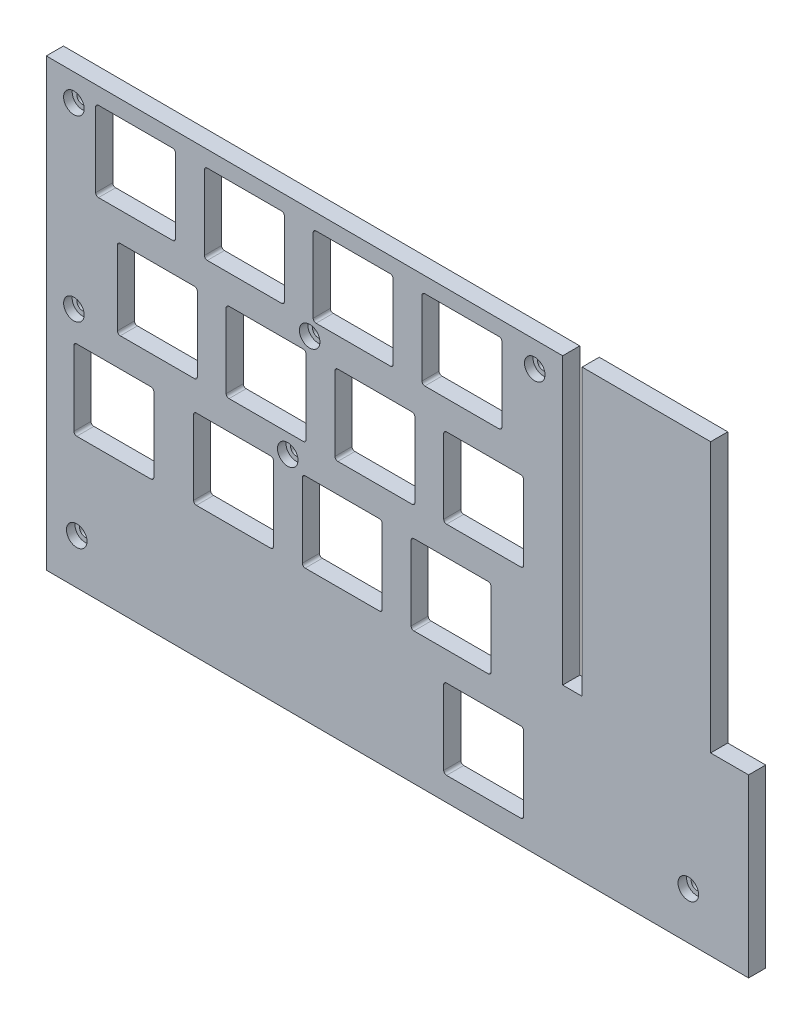
SolidWorks part; units mm, degrees
ref_plane "Front Plane" through (0, 0, 0) normal (0, 0, 1) x (1, 0, 0)
ref_plane "Top Plane" through (0, 0, 0) normal (0, 1, 0) x (1, 0, 0)
ref_plane "Right Plane" through (0, 0, 0) normal (1, 0, 0) x (0, 0, -1)
sketch "Model" plane through (0, 0, 0) normal (0, 0, 1) x (1, 0, 0)
  line L0 (9.145, -2.923) -> (22.145, -2.923)
  line L1 (9.145, -16.923) -> (22.145, -16.923)
  line L2 (8.645, -3.423) -> (8.645, -16.423)
  line L3 (22.645, -3.423) -> (22.645, -16.423)
  line L4 (28.195, -2.923) -> (41.195, -2.923)
  line L5 (28.195, -16.923) -> (41.195, -16.923)
  line L6 (27.695, -3.423) -> (27.695, -16.423)
  line L7 (41.695, -3.423) -> (41.695, -16.423)
  line L8 (47.245, -2.923) -> (60.245, -2.923)
  line L9 (47.245, -16.923) -> (60.245, -16.923)
  line L10 (46.745, -3.423) -> (46.745, -16.423)
  line L11 (60.745, -3.423) -> (60.745, -16.423)
  line L12 (66.295, -2.923) -> (79.295, -2.923)
  line L13 (66.295, -16.923) -> (79.295, -16.923)
  line L14 (65.795, -3.423) -> (65.795, -16.423)
  line L15 (79.795, -3.423) -> (79.795, -16.423)
  line L16 (12.955, -21.973) -> (25.955, -21.973)
  line L17 (12.955, -35.973) -> (25.955, -35.973)
  line L18 (12.455, -22.473) -> (12.455, -35.473)
  line L19 (26.455, -22.473) -> (26.455, -35.473)
  line L20 (32.005, -21.973) -> (45.005, -21.973)
  line L21 (32.005, -35.973) -> (45.005, -35.973)
  line L22 (31.505, -22.473) -> (31.505, -35.473)
  line L23 (45.505, -22.473) -> (45.505, -35.473)
  line L24 (51.055, -21.973) -> (64.055, -21.973)
  line L25 (51.055, -35.973) -> (64.055, -35.973)
  line L26 (50.555, -22.473) -> (50.555, -35.473)
  line L27 (64.555, -22.473) -> (64.555, -35.473)
  line L28 (70.105, -21.973) -> (83.105, -21.973)
  line L29 (70.105, -35.973) -> (83.105, -35.973)
  line L30 (69.605, -22.473) -> (69.605, -35.473)
  line L31 (83.605, -22.473) -> (83.605, -35.473)
  line L32 (5.335, -41.023) -> (18.335, -41.023)
  line L33 (5.335, -55.023) -> (18.335, -55.023)
  line L34 (4.835, -41.523) -> (4.835, -54.523)
  line L35 (18.835, -41.523) -> (18.835, -54.523)
  line L36 (26.29, -41.023) -> (39.29, -41.023)
  line L37 (26.29, -55.023) -> (39.29, -55.023)
  line L38 (25.79, -41.523) -> (25.79, -54.523)
  line L39 (39.79, -41.523) -> (39.79, -54.523)
  line L40 (45.34, -41.023) -> (58.34, -41.023)
  line L41 (45.34, -55.023) -> (58.34, -55.023)
  line L42 (44.84, -41.523) -> (44.84, -54.523)
  line L43 (58.84, -41.523) -> (58.84, -54.523)
  line L44 (64.39, -41.023) -> (77.39, -41.023)
  line L45 (64.39, -55.023) -> (77.39, -55.023)
  line L46 (63.89, -41.523) -> (63.89, -54.523)
  line L47 (77.89, -41.523) -> (77.89, -54.523)
  line L48 (70.105, -60.073) -> (83.105, -60.073)
  line L49 (70.105, -74.073) -> (83.105, -74.073)
  line L50 (69.605, -60.573) -> (69.605, -73.573)
  line L51 (83.605, -60.573) -> (83.605, -73.573)
  line L52 (61.667, -61.073) -> (67.667, -61.073)
  line L53 (61.667, -76.073) -> (67.667, -76.073)
  line L54 (61.167, -61.573) -> (61.167, -75.573)
  line L55 (68.167, -61.573) -> (68.167, -75.573)
  line L56 (85.543, -61.073) -> (91.543, -61.073)
  line L57 (85.543, -76.073) -> (91.543, -76.073)
  line L58 (85.043, -61.573) -> (85.043, -75.573)
  line L59 (92.043, -61.573) -> (92.043, -75.573)
  line L60 (0, -78) -> (123, -78.3615)
  line L61 (0, 0) -> (123, -0.3615)
  line L62 (0, -78) -> (0, 0)
  line L63 (123, -78.3615) -> (123, -0.3615)
  line L64 (27.8414, -16.7766) -> (26.3085, -22.1195) construction
  line L65 (46.8914, -16.7766) -> (45.3585, -22.1195) construction
  line L67 (64.055, -35.973) -> (58.34, -41.023) construction
  line L69 (25.955, -35.973) -> (18.335, -41.023) construction
  arc A0 (9.145, -2.923) -> (8.645, -3.423) centre (9.145, -3.423) ccw
  arc A1 (22.645, -3.423) -> (22.145, -2.923) centre (22.145, -3.423) ccw
  arc A2 (8.645, -16.423) -> (9.145, -16.923) centre (9.145, -16.423) ccw
  arc A3 (22.145, -16.923) -> (22.645, -16.423) centre (22.145, -16.423) ccw
  arc A4 (28.195, -2.923) -> (27.695, -3.423) centre (28.195, -3.423) ccw
  arc A5 (41.695, -3.423) -> (41.195, -2.923) centre (41.195, -3.423) ccw
  arc A6 (27.695, -16.423) -> (28.195, -16.923) centre (28.195, -16.423) ccw
  arc A7 (41.195, -16.923) -> (41.695, -16.423) centre (41.195, -16.423) ccw
  arc A8 (47.245, -2.923) -> (46.745, -3.423) centre (47.245, -3.423) ccw
  arc A9 (60.745, -3.423) -> (60.245, -2.923) centre (60.245, -3.423) ccw
  arc A10 (46.745, -16.423) -> (47.245, -16.923) centre (47.245, -16.423) ccw
  arc A11 (60.245, -16.923) -> (60.745, -16.423) centre (60.245, -16.423) ccw
  arc A12 (66.295, -2.923) -> (65.795, -3.423) centre (66.295, -3.423) ccw
  arc A13 (79.795, -3.423) -> (79.295, -2.923) centre (79.295, -3.423) ccw
  arc A14 (65.795, -16.423) -> (66.295, -16.923) centre (66.295, -16.423) ccw
  arc A15 (79.295, -16.923) -> (79.795, -16.423) centre (79.295, -16.423) ccw
  arc A16 (12.955, -21.973) -> (12.455, -22.473) centre (12.955, -22.473) ccw
  arc A17 (26.455, -22.473) -> (25.955, -21.973) centre (25.955, -22.473) ccw
  arc A18 (12.455, -35.473) -> (12.955, -35.973) centre (12.955, -35.473) ccw
  arc A19 (25.955, -35.973) -> (26.455, -35.473) centre (25.955, -35.473) ccw
  arc A20 (32.005, -21.973) -> (31.505, -22.473) centre (32.005, -22.473) ccw
  arc A21 (45.505, -22.473) -> (45.005, -21.973) centre (45.005, -22.473) ccw
  arc A22 (31.505, -35.473) -> (32.005, -35.973) centre (32.005, -35.473) ccw
  arc A23 (45.005, -35.973) -> (45.505, -35.473) centre (45.005, -35.473) ccw
  arc A24 (51.055, -21.973) -> (50.555, -22.473) centre (51.055, -22.473) ccw
  arc A25 (64.555, -22.473) -> (64.055, -21.973) centre (64.055, -22.473) ccw
  arc A26 (50.555, -35.473) -> (51.055, -35.973) centre (51.055, -35.473) ccw
  arc A27 (64.055, -35.973) -> (64.555, -35.473) centre (64.055, -35.473) ccw
  arc A28 (70.105, -21.973) -> (69.605, -22.473) centre (70.105, -22.473) ccw
  arc A29 (83.605, -22.473) -> (83.105, -21.973) centre (83.105, -22.473) ccw
  arc A30 (69.605, -35.473) -> (70.105, -35.973) centre (70.105, -35.473) ccw
  arc A31 (83.105, -35.973) -> (83.605, -35.473) centre (83.105, -35.473) ccw
  arc A32 (5.335, -41.023) -> (4.835, -41.523) centre (5.335, -41.523) ccw
  arc A33 (18.835, -41.523) -> (18.335, -41.023) centre (18.335, -41.523) ccw
  arc A34 (4.835, -54.523) -> (5.335, -55.023) centre (5.335, -54.523) ccw
  arc A35 (18.335, -55.023) -> (18.835, -54.523) centre (18.335, -54.523) ccw
  arc A36 (26.29, -41.023) -> (25.79, -41.523) centre (26.29, -41.523) ccw
  arc A37 (39.79, -41.523) -> (39.29, -41.023) centre (39.29, -41.523) ccw
  arc A38 (25.79, -54.523) -> (26.29, -55.023) centre (26.29, -54.523) ccw
  arc A39 (39.29, -55.023) -> (39.79, -54.523) centre (39.29, -54.523) ccw
  arc A40 (45.34, -41.023) -> (44.84, -41.523) centre (45.34, -41.523) ccw
  arc A41 (58.84, -41.523) -> (58.34, -41.023) centre (58.34, -41.523) ccw
  arc A42 (44.84, -54.523) -> (45.34, -55.023) centre (45.34, -54.523) ccw
  arc A43 (58.34, -55.023) -> (58.84, -54.523) centre (58.34, -54.523) ccw
  arc A44 (64.39, -41.023) -> (63.89, -41.523) centre (64.39, -41.523) ccw
  arc A45 (77.89, -41.523) -> (77.39, -41.023) centre (77.39, -41.523) ccw
  arc A46 (63.89, -54.523) -> (64.39, -55.023) centre (64.39, -54.523) ccw
  arc A47 (77.39, -55.023) -> (77.89, -54.523) centre (77.39, -54.523) ccw
  arc A48 (70.105, -60.073) -> (69.605, -60.573) centre (70.105, -60.573) ccw
  arc A49 (83.605, -60.573) -> (83.105, -60.073) centre (83.105, -60.573) ccw
  arc A50 (69.605, -73.573) -> (70.105, -74.073) centre (70.105, -73.573) ccw
  arc A51 (83.105, -74.073) -> (83.605, -73.573) centre (83.105, -73.573) ccw
  arc A52 (61.667, -61.073) -> (61.167, -61.573) centre (61.667, -61.573) ccw
  arc A53 (68.167, -61.573) -> (67.667, -61.073) centre (67.667, -61.573) ccw
  arc A54 (61.167, -75.573) -> (61.667, -76.073) centre (61.667, -75.573) ccw
  arc A55 (67.667, -76.073) -> (68.167, -75.573) centre (67.667, -75.573) ccw
  arc A56 (85.543, -61.073) -> (85.043, -61.573) centre (85.543, -61.573) ccw
  arc A57 (92.043, -61.573) -> (91.543, -61.073) centre (91.543, -61.573) ccw
  arc A58 (85.043, -75.573) -> (85.543, -76.073) centre (85.543, -75.573) ccw
  arc A59 (91.543, -76.073) -> (92.043, -75.573) centre (91.543, -75.573) ccw
  circle A60 centre (4.835, -4.704) radius 1
  circle A62 centre (46.125, -19.448) radius 1
  circle A63 centre (85.543, -4.704) radius 1.8
  circle A66 centre (42.2863, -39.2998) radius 1
  circle A68 centre (4.835, -35.973) radius 1
  circle A69 centre (4.835, -4.704) radius 1.8
  circle A71 centre (46.125, -19.448) radius 1.8
  circle A72 centre (85.543, -4.704) radius 1
  circle A75 centre (42.2863, -39.2998) radius 1.8
  circle A77 centre (4.835, -35.973) radius 1.8
  circle A78 centre (5.335, -70.1004) radius 1.8
  circle A79 centre (5.335, -70.1004) radius 1
  circle A80 centre (112.442, -70.1004) radius 1.8
  circle A81 centre (112.442, -70.1004) radius 1
  point P186 (6.071, -20.0378)
  point P187 (6.071, -36.7083)
  point P192 (4.835, -4.653)
  point P194 (4.835, -35.973)
  point P195 (5.7443, -70.7637)
  point P200 (5.335, -70.1004)
  point P201 (0, 0)
  point P202 (85.543, -4.704)
  point P207 (4.835, -4.704)
  point P211 (0, 0)
  point P214 (0, 0)
  dimension "D3" = 2
  dimension "D4" = 3.6
  dimension "D1" = 78
  dimension "D2" = 123
extrude "Boss-Extrude1" add sketch "Model" along normal blind 3 contours L60 L63 L61 L62 A77 A75 A71 A69 A63 A59 L57 A58 L58 A56 L56 A57 L59 A55 L53 A54 L54 A52 L52 A53 L55 A51 L49 A50 L50 A48 L48 A49 L51 A47 | A77 A68 | A75 A66 | A63 A72 | A71 A62 | A69 A60 | A80 A81 | A78 A79 | L53 A55 L55 A53 L52 A52 L54 A54 | L57 A59 L59 A57 L56 A56 L58 A58 region at (64.667, -68.573, 0) region at (88.543, -68.573, 0) region at (1.4584, -39, 0) region at (83.7939, -4.704, 0) region at (3.0859, -4.704, 0) region at (44.3759, -19.448, 0) region at (40.5372, -39.2998, 0) region at (3.0859, -35.973, 0) region at (3.5859, -70.1004, 0) region at (110.6929, -70.1004, 0)
extrude "Cut-Extrude1" cut sketch "Model<3>" against normal blind 1.5 from surface contours A69 | A71 | A63 | A77 | A75 | A78 | A80 starting at face at (76.605, -67.073, 3)
sketch "Model<3>" plane through (0, 0, 0) normal (0, 0, 1) x (1, 0, 0) same geometry as "Model"
sketch "Sketch3" plane through (0, 0, 3) normal (0, 0, 1) x (1, 0, 0)
  line L0 (0, 0) -> (123, -0.3615) construction
  line L1 (90.4342, -0.2658) -> (93.8447, -0.2658)
  line L2 (90.4342, -0.2658) -> (90.4342, -50.2113)
  line L3 (90.4342, -50.2113) -> (93.8447, -50.2113)
  line L4 (93.8447, -0.2658) -> (93.8447, -50.2113)
  line L5 (123, -78.3615) -> (123, -0.3615) construction
  line L6 (116.3518, -0.3419) -> (123, -0.3419)
  line L7 (116.3518, -0.3419) -> (116.3518, -47.5526)
  line L8 (116.3518, -47.5526) -> (123, -47.5526)
  line L9 (123, -0.3419) -> (123, -47.5526)
extrude "Cut-Extrude2" cut sketch "Sketch3" against normal blind 5
sketch "Sketch4" plane through (0, 0, 0) normal (0, 0, 1) x (1, 0, 0)
  circle A0 centre (104.7576, -16.1304) radius 3.5444
  circle A1 centre (104.7576, -16.1304) radius 2.3691
extrude "Boss-Extrude2" add sketch "Sketch4" against normal blind 7
